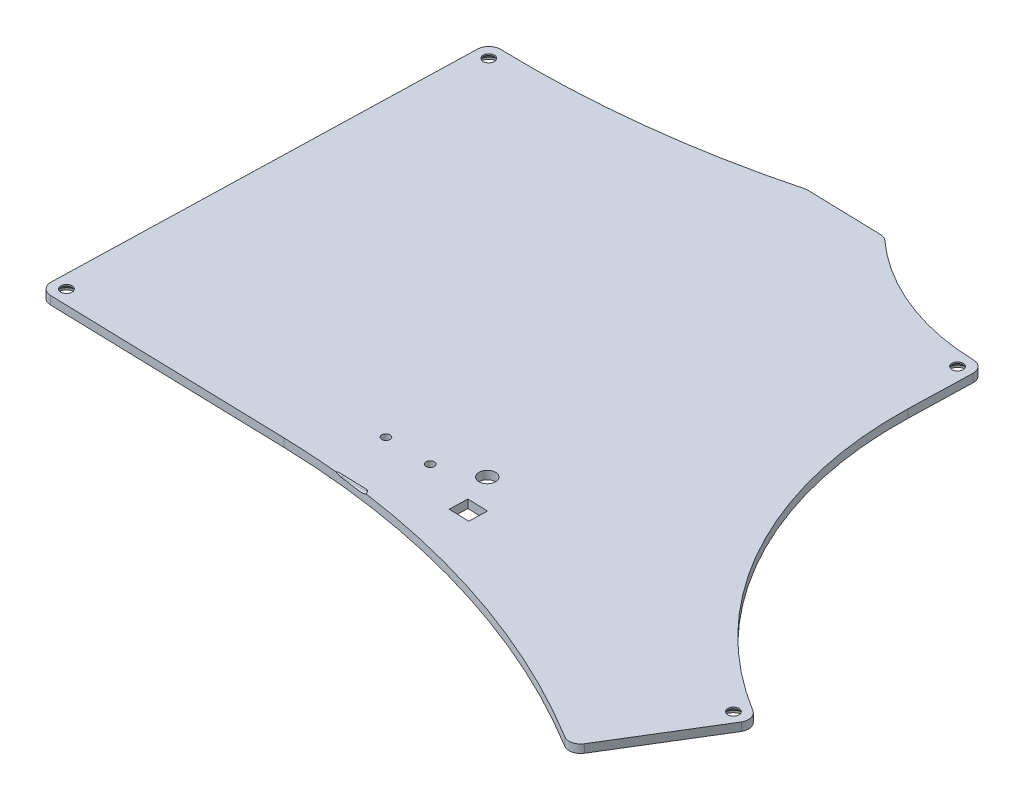
SolidWorks part; units mm, degrees
ref_plane "Front Plane" through (0, 0, 0) normal (0, 0, 1) x (1, 0, 0)
ref_plane "Top Plane" through (0, 0, 0) normal (0, 1, 0) x (1, 0, 0)
ref_plane "Right Plane" through (0, 0, 0) normal (1, 0, 0) x (0, 0, -1)
sketch "Main" plane through (0, 0, 0) normal (0, 1, 0) x (1, 0, 0)
  line L13 (-10.5797, -88.3991) -> (-6.2814, -88.5178) construction
  line L18 (-10.8741, -88.1909) -> (-5.976, -88.3262) construction
  line L19 (-10.8741, -88.1909) -> (-10.9955, -92.5892) construction
  line L20 (-5.976, -88.3262) -> (-6.0974, -92.7245) construction
  line L21 (-10.9955, -92.5892) -> (-6.0974, -92.7245) construction
  line L22 (-10.7873, -92.2949) -> (-10.6824, -88.4963) construction
  line L23 (-6.1842, -88.6205) -> (-6.2891, -92.4191) construction
  line L26 (-6.3918, -92.5163) -> (-10.6901, -92.3976) construction
  line L69 (-104.2231, 7.3223) -> (-106.9973, -93.1394)
  line L70 (-16.4114, 17.4022) -> (-34.4046, 17.899)
  line L71 (23.6817, -16.0031) -> (24.1037, -0.7231)
  line L72 (54.716, -125.4699) -> (69.1643, -101.872)
  line L73 (-104.0813, -96.2211) -> (-45.8908, -97.828)
  line L74 (-104.2231, 7.3223) -> (-106.9973, -93.1394) construction
  line L75 (-16.4114, 17.4022) -> (-34.4046, 17.899) construction
  line L76 (23.6817, -16.0031) -> (24.1037, -0.7231) construction
  line L77 (54.716, -125.4699) -> (69.1643, -101.872) construction
  line L78 (-104.0813, -96.2211) -> (-45.8908, -97.828) construction
  circle A11 centre (-13.1327, -81.2259) radius 1.5 construction
  circle A19 centre (-13.1327, -81.2259) radius 1.5 construction
  circle A24 centre (65.8328, -100.6104) radius 1.35 construction
  circle A25 centre (-103.4848, -92.7362) radius 1.35 construction
  circle A26 centre (-100.7383, 6.7264) radius 1.35 construction
  circle A27 centre (20.5913, -1.1242) radius 1.35 construction
  circle A28 centre (-100.7383, 6.7264) radius 1.35 construction
  circle A125 centre (-22.7527, -85.442) radius 1 construction
  circle A126 centre (-33.7485, -85.1383) radius 1 construction
  arc A135 (-106.9973, -93.1394) -> (-104.0813, -96.2211) centre (-103.9985, -93.2222) ccw
  arc A136 (-101.1415, 10.2383) -> (-104.2231, 7.3223) centre (-101.2243, 7.2395) ccw
  arc A137 (-101.1415, 10.2383) -> (-35.2476, 17.8023) centre (-94.6684, 244.649) ccw
  arc A138 (-34.4046, 17.899) -> (-35.2476, 17.8023) centre (-34.4874, 14.9002) ccw
  arc A139 (-14.4856, 16.6317) -> (-16.4114, 17.4022) centre (-16.4942, 14.4033) ccw
  arc A140 (-14.4856, 16.6317) -> (21.1876, 2.3586) centre (22.7216, 57.9088) ccw
  arc A141 (24.1037, -0.7231) -> (21.1876, 2.3586) centre (21.1048, -0.6403) ccw
  arc A142 (23.6817, -16.0031) -> (68.0862, -97.8876) centre (116.6499, -18.5703) ccw
  arc A143 (69.1643, -101.872) -> (68.0862, -97.8876) centre (66.5172, -100.4502) ccw
  arc A144 (50.591, -126.4619) -> (54.716, -125.4699) centre (52.1575, -123.9034) ccw
  arc A145 (50.591, -126.4619) -> (-45.8908, -97.828) centre (-51.2758, -292.8371) ccw
  arc A146 (-106.9973, -93.1394) -> (-104.0813, -96.2211) centre (-103.9985, -93.2222) ccw construction
  arc A147 (-101.1415, 10.2383) -> (-104.2231, 7.3223) centre (-101.2243, 7.2395) ccw construction
  arc A148 (-101.1415, 10.2383) -> (-35.2476, 17.8023) centre (-94.6684, 244.649) ccw construction
  arc A149 (-34.4046, 17.899) -> (-35.2476, 17.8023) centre (-34.4874, 14.9002) ccw construction
  arc A150 (-14.4856, 16.6317) -> (-16.4114, 17.4022) centre (-16.4942, 14.4033) ccw construction
  arc A151 (-14.4856, 16.6317) -> (21.1876, 2.3586) centre (22.7216, 57.9088) ccw construction
  arc A152 (24.1037, -0.7231) -> (21.1876, 2.3586) centre (21.1048, -0.6403) ccw construction
  arc A153 (23.6817, -16.0031) -> (68.0862, -97.8876) centre (116.6499, -18.5703) ccw construction
  arc A154 (69.1643, -101.872) -> (68.0862, -97.8876) centre (66.5172, -100.4502) ccw construction
  arc A155 (50.591, -126.4619) -> (54.716, -125.4699) centre (52.1575, -123.9034) ccw construction
  arc A156 (50.591, -126.4619) -> (-45.8908, -97.828) centre (-51.2758, -292.8371) ccw construction
  dimension "D2" = 3
  dimension "D3" = 2
  dimension "D4" = 0.2
  dimension "D5" = 0.2
  dimension "D6" = 0.2
  dimension "D7" = 0.2
  dimension "D1" = 0
sketch "Sketch7" plane through (0, 0, 0) normal (0, 1, 0) x (1, 0, 0)
  line L0 (-10.8741, -88.1909) -> (-5.976, -88.3262)
  line L1 (-5.976, -88.3262) -> (-6.0974, -92.7245)
  line L2 (-6.0974, -92.7245) -> (-10.9955, -92.5892)
  line L3 (-10.9955, -92.5892) -> (-10.8741, -88.1909)
  line L42 (-104.0232, 7.3167) -> (-106.7974, -93.145)
  line L43 (-104.0757, -96.0212) -> (-45.8853, -97.6281)
  line L44 (54.5454, -125.3654) -> (68.9908, -101.7724)
  line L45 (23.4818, -15.9975) -> (23.9038, -0.7176)
  line L46 (-16.417, 17.2023) -> (-34.4101, 17.6991)
  line L47 (-104.0232, 7.3167) -> (-106.7974, -93.145)
  line L48 (-104.0757, -96.0212) -> (-45.8853, -97.6281)
  line L49 (54.5454, -125.3654) -> (68.9908, -101.7724)
  line L50 (23.4818, -15.9975) -> (23.9038, -0.7176)
  line L51 (-16.417, 17.2023) -> (-34.4101, 17.6991)
  circle A0 centre (-33.7485, -85.1383) radius 1
  circle A1 centre (-22.7527, -85.442) radius 1
  circle A2 centre (-13.1327, -81.2259) radius 2
  circle A3 centre (-33.7485, -85.1383) radius 1 construction
  circle A5 centre (-103.4848, -92.7362) radius 1.35
  circle A6 centre (-100.7383, 6.7264) radius 1.35
  circle A7 centre (20.5913, -1.1242) radius 1.35
  circle A8 centre (65.8328, -100.6104) radius 1.35
  circle A9 centre (65.8328, -100.6104) radius 1.35 construction
  arc A110 (-101.147, 10.0384) -> (-104.0232, 7.3167) centre (-101.2243, 7.2395) ccw
  arc A111 (-106.7974, -93.145) -> (-104.0757, -96.0212) centre (-103.9985, -93.2222) ccw
  arc A112 (50.6954, -126.2913) -> (-45.8853, -97.6281) centre (-51.2758, -292.8371) ccw
  arc A113 (50.6954, -126.2913) -> (54.5454, -125.3654) centre (52.1575, -123.9034) ccw
  arc A114 (68.9908, -101.7724) -> (67.9817, -98.0582) centre (66.5172, -100.4502) ccw
  arc A115 (23.4818, -15.9975) -> (67.9817, -98.0582) centre (116.6499, -18.5703) ccw
  arc A116 (23.9038, -0.7176) -> (21.1821, 2.1586) centre (21.1048, -0.6403) ccw
  arc A117 (-14.6195, 16.4831) -> (21.1821, 2.1586) centre (22.7216, 57.9088) ccw
  arc A118 (-14.6195, 16.4831) -> (-16.417, 17.2023) centre (-16.4942, 14.4033) ccw
  arc A119 (-34.4101, 17.6991) -> (-35.1969, 17.6088) centre (-34.4874, 14.9002) ccw
  arc A120 (-101.147, 10.0384) -> (-35.1969, 17.6088) centre (-94.6684, 244.649) ccw
  arc A121 (-101.147, 10.0384) -> (-104.0232, 7.3167) centre (-101.2243, 7.2395) ccw
  arc A122 (-106.7974, -93.145) -> (-104.0757, -96.0212) centre (-103.9985, -93.2222) ccw
  arc A123 (50.6954, -126.2913) -> (-45.8853, -97.6281) centre (-51.2758, -292.8371) ccw
  arc A124 (50.6954, -126.2913) -> (54.5454, -125.3654) centre (52.1575, -123.9034) ccw
  arc A125 (68.9908, -101.7724) -> (67.9817, -98.0582) centre (66.5172, -100.4502) ccw
  arc A126 (23.4818, -15.9975) -> (67.9817, -98.0582) centre (116.6499, -18.5703) ccw
  arc A127 (23.9038, -0.7176) -> (21.1821, 2.1586) centre (21.1048, -0.6403) ccw
  arc A128 (-14.6195, 16.4831) -> (21.1821, 2.1586) centre (22.7216, 57.9088) ccw
  arc A129 (-14.6195, 16.4831) -> (-16.417, 17.2023) centre (-16.4942, 14.4033) ccw
  arc A130 (-34.4101, 17.6991) -> (-35.1969, 17.6088) centre (-34.4874, 14.9002) ccw
  arc A131 (-101.147, 10.0384) -> (-35.1969, 17.6088) centre (-94.6684, 244.649) ccw
  dimension "D2" = 4
  dimension "D1" = 0.2
extrude "Main_plate" add sketch "Sketch7" against normal blind 2
ref_plane "Charge_port_plane1" through (-2.7344, 0, 99.0197) normal (-0.0276, 0, 0.9996) x (0.9996, 0, 0.0276)
ref_plane "Charge_port_plane2" through (-2.8724, 0, 104.0178) normal (-0.0276, 0, 0.9996) x (0.9996, 0, 0.0276)
sketch "Sketch8" plane through (-2.7344, 0, 99.0197) normal (-0.0276, 0, 0.9996) x (0.9996, 0, 0.0276)
  line L0 (-28.2855, 3.5) -> (-23.4855, 3.5) construction
  line L1 (-28.2855, 6.75) -> (-23.4855, 6.75) construction
  line L2 (-28.2855, 0.25) -> (-23.4855, 0.25) construction
  line L3 (-104.1855, -2) -> (-104.1855, 0) construction
  line L4 (-101.3855, -2) -> (-43.1729, -2) construction
  line L5 (-28.2855, 7.25) -> (-23.4855, 7.25)
  line L6 (-28.2855, -0.25) -> (-23.4855, -0.25)
  arc A0 (-28.2855, 6.75) -> (-28.2855, 0.25) centre (-28.2855, 3.5) ccw construction
  arc A1 (-23.4855, 0.25) -> (-23.4855, 6.75) centre (-23.4855, 3.5) ccw construction
  arc A2 (-23.4855, -0.25) -> (-23.4855, 7.25) centre (-23.4855, 3.5) ccw
  arc A3 (-28.2855, 7.25) -> (-28.2855, -0.25) centre (-28.2855, 3.5) ccw
  point P2 (-25.8855, 3.5)
  dimension "D5" = 0.5
  dimension "D1" = 4.8
  dimension "D2" = 6.5
  dimension "D3" = 78.3
  dimension "D4" = 5.5
sketch "Sketch9" plane through (-2.8724, 0, 104.0178) normal (-0.0276, 0, 0.9996) x (0.9996, 0, 0.0276)
  line L4 (-28.2855, -1.75) -> (-23.4855, -1.75)
  line L5 (-23.4855, 8.75) -> (-28.2855, 8.75)
  line L6 (-28.2855, -1.75) -> (-23.4855, -1.75)
  line L7 (-23.4855, 8.75) -> (-28.2855, 8.75)
  arc A4 (-28.2855, 8.75) -> (-28.2855, -1.75) centre (-28.2855, 3.5) ccw
  arc A5 (-23.4855, -1.75) -> (-23.4855, 8.75) centre (-23.4855, 3.5) ccw
  arc A6 (-28.2855, 8.75) -> (-28.2855, -1.75) centre (-28.2855, 3.5) ccw
  arc A7 (-23.4855, -1.75) -> (-23.4855, 8.75) centre (-23.4855, 3.5) ccw
  dimension "D1" = 1.5
loft "Charge_port" cut profiles "Sketch8", "Sketch9"
fillet "Charge_port_fllet" radius 0.3 3 edges
sketch "Sketch10" plane through (0, -2, 0) normal (0, -1, 0) x (1, 0, 0)
  circle A0 centre (-103.4848, 92.7362) radius 2.5
  circle A1 centre (65.8328, 100.6104) radius 2.5
  circle A2 centre (20.5913, 1.1242) radius 2.5
  circle A3 centre (-100.7383, -6.7264) radius 2.5
  dimension "D1" = 5
extrude "Screw_holes" cut sketch "Sketch10" against normal blind 1.7
chamfer "Screw_holes_chamfer" distance 1.2 angle 45 4 edges at (65.8328, -0.3, 98.1104) (-103.4848, -0.3, 90.2362) (-100.7383, -0.3, -9.2264) (20.5913, -0.3, -1.3758)
